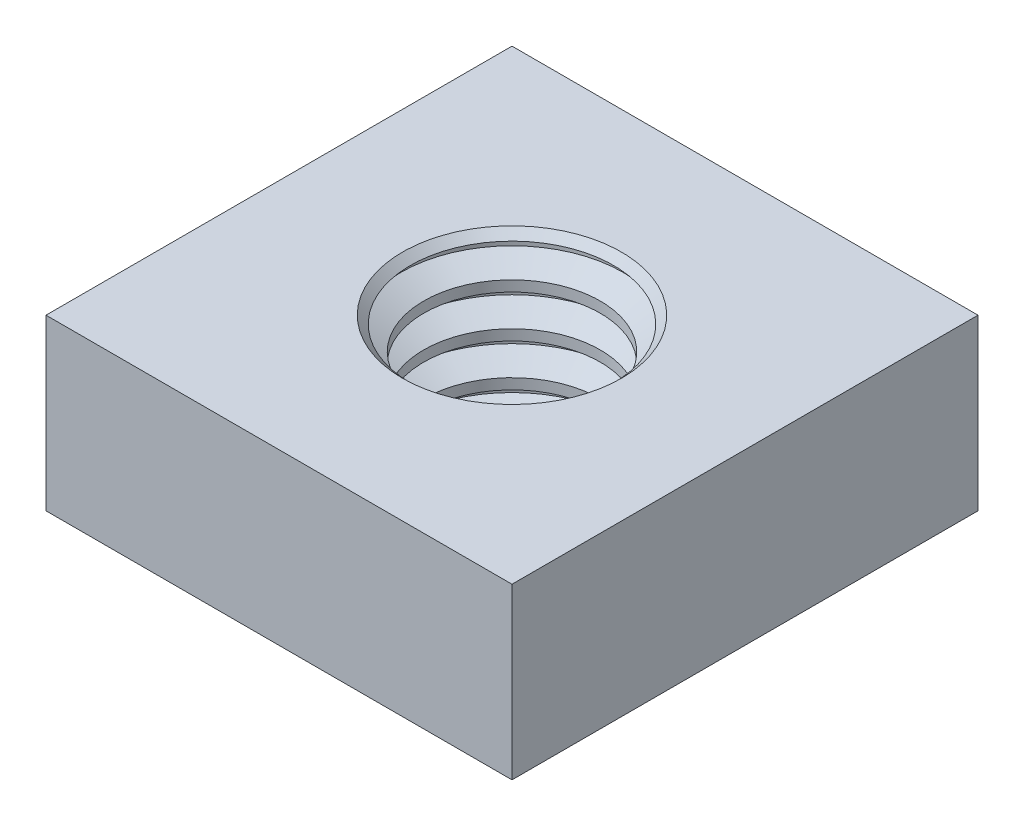
SolidWorks part; units mm, degrees
ref_plane "Front" through (0, 0, 0) normal (0, 0, 1) x (1, 0, 0)
ref_plane "Top" through (0, 0, 0) normal (0, 1, 0) x (1, 0, 0)
ref_plane "Right" through (0, 0, 0) normal (1, 0, 0) x (0, 0, -1)
sketch "Sketch1" plane through (0, 0, 0) normal (0, 1, 0) x (1, 0, 0)
  line L0 (-18.2415, -5.4908) -> (-20.2259, -6.6365) [skipped]
  line L1 (18.2415, -5.4908) -> (16.2572, -4.3451) [skipped]
  line L2 (-4.3656, 4.3656) -> (-4.3656, -4.3656)
  line L3 (0, -5.041) -> (1.9844, -3.8953) [skipped]
  line L4 (-4.3656, 4.3656) -> (4.3656, 4.3656)
  line L5 (4.3656, -4.3656) -> (4.3656, 4.3656)
  line L6 (-4.3656, -2.5205) -> (-2.3812, -3.6662) [skipped]
  line L9 (-4.3656, -4.3656) -> (4.3656, -4.3656)
  circle A0 centre (0, 0) radius 4.3656 construction
  dimension "Hex Flats" = 8.7312
extrude "Extrude1" add sketch "Sketch1" along normal blind 3.175
ref_axis "Axis1" through (0, 3.3337, 0) along (0, -1, 0)
ref_plane "Plane1" through (0, 0, 0) normal (0.7071, 0, 0.7071) x (0.7071, 0, -0.7071)
sketch "Sketch2" plane through (0, 0, 0) normal (0, 0, 1) x (1, 0, 0)
  line L0 (0, 1.6636) -> (0, -0.3796) construction
  line L1 (0, 3.175) -> (1.6532, 3.175)
  line L3 (-4.3656, 3.175) -> (4.3656, 3.175) construction
  line L4 (0, 2.3812) -> (1.6532, 2.3812)
  line L5 (1.6532, 3.175) -> (2.0828, 2.927)
  line L6 (2.0828, 2.927) -> (2.0828, 2.8277)
  line L7 (2.0828, 2.8277) -> (1.6532, 2.5797)
  line L9 (1.6532, 2.3812) -> (1.6532, 2.5797)
  line L10 (0, 2.3812) -> (0, 3.175)
  line L11 (1.6532, 3.175) -> (1.6532, 2.5797) construction
  line L12 (2.0828, 2.8773) -> (1.6532, 2.8773) construction
  dimension "D1" = 60
  dimension "D2" = 0.1984
  dimension "D5" = 0.0992
  dimension "Pitch" = 0.7937
  dimension "Major Dia." = 4.1656
revolve "Cut-Revolve1" cut sketch "Sketch2" angle 360 about L0
pattern_linear "LPattern2" count 5 spacing 0.7937 along (0, -1, 0) of "Cut-Revolve1"
chamfer "Chamfer1" distance 0.3969 angle 45 1 edges at (0, 3.175, 1.6532) first distance on face at (0, 3.175, 0)
equation "\"D5@Sketch2\"=\"Pitch@Sketch2\"/8"
equation "\"D2@Sketch2\"=\"Pitch@Sketch2\"/4"
equation "\"D3@LPattern2\"=\"Pitch@Sketch2\""
equation "\"D1@LPattern2\"=int(\"Height@Extrude1\"/\"Pitch@Sketch2\")+1"
equation "\"D1@Chamfer1\"=\"Pitch@Sketch2\"/2"
